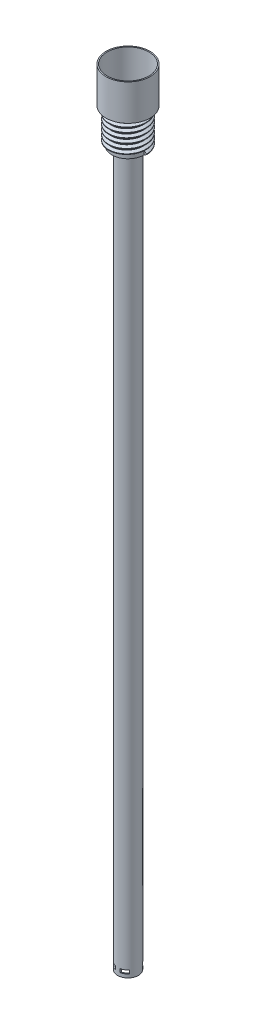
SolidWorks part; units mm, degrees
material "PVC Rigid"
ref_plane "Front Plane" through (0, 0, 0) normal (0, 0, 1) x (1, 0, 0)
ref_plane "Top Plane" through (0, 0, 0) normal (0, 1, 0) x (1, 0, 0)
ref_plane "Right Plane" through (0, 0, 0) normal (1, 0, 0) x (0, 0, -1)
sketch "Sketch1" plane through (0, 0, 0) normal (0, 0, 1) x (1, 0, 0)
  line L0 (0, 450) -> (-18, 450)
  line L1 (-18, 450) -> (-18, 420)
  line L3 (-8, 390) -> (-8, -227)
  line L4 (-8, -227) -> (0, -227)
  line L5 (0, -227) -> (0, 450)
  line L6 (-18, 420) -> (-13, 420)
  line L7 (-13, 420) -> (-13, 390)
  line L8 (-13, 390) -> (-8, 390)
  line L11 (-181.4716, -232) -> (43.7489, -232) construction
  dimension "D1" = 5
  dimension "D3" = 18
  dimension "D4" = 60
  dimension "D5" = 30
  dimension "D6" = 5
revolve "Revolve1" add sketch "Sketch1" angle 360 about L5
shell "Shell1" thickness 1 removed face at (8, -227, 0) removed face at (18, 450, 0) outward yes
thread "Thread1" pitch 4 method extrude profile "Thread Profile1" start angle 0, offset 0, length 30, pitch 4, diameter 28
ref_plane "Plane1" through (14, 389, 0) normal (0, 0, 1) x (1, 0, 0)
sketch "Thread Profile1" plane through (14, 389, 0) normal (0, 0, 1) x (1, 0, 0)
  line L0 (0, 0) -> (0, 4) construction
  line L1 (0, 0) -> (2.1651, 1.25)
  line L2 (2.1651, 1.25) -> (2.1651, 1.75)
  line L3 (2.1651, 1.75) -> (0, 3)
  line L4 (2.1651, 1.5) -> (0, 1.5) construction
  line L11 (0, 0) -> (0, 3)
  point P2 (0, 0)
  dimension "Pitch" = 4
  dimension "Profile_Angle" = 60
  dimension "Profile_Land" = 0.5
  dimension "Profile_Height" = 2.1651
sketch "Sketch5" plane through (0, 0, 0) normal (0, 0, 1) x (1, 0, 0)
  line L0 (0, 0) -> (0, 14.277) construction
  line L1 (2, -224) -> (7, -224)
  line L2 (2, -224) -> (2, -221)
  line L3 (2, -221) -> (7, -221)
  line L4 (7, -224) -> (7, -221)
  line L5 (2, -224) -> (7, -221) construction
  line L6 (2, -221) -> (7, -224) construction
  line L7 (-2, -221) -> (-7, -224) construction
  line L8 (-2, -224) -> (-7, -221) construction
  line L9 (-7, -224) -> (-7, -221)
  line L10 (-2, -221) -> (-7, -221)
  line L11 (-2, -224) -> (-2, -221)
  line L12 (-2, -224) -> (-7, -224)
  line L13 (-8, -227) -> (8, -227) construction
  point P4 (4.5, -222.5)
  point P12 (-4.5, -222.5)
  dimension "D1" = 3
  dimension "D2" = 7
  dimension "D3" = 2
  dimension "D4" = 3
extrude "Cut-Extrude1" cut sketch "Sketch5" against normal through all both and the other way through all
